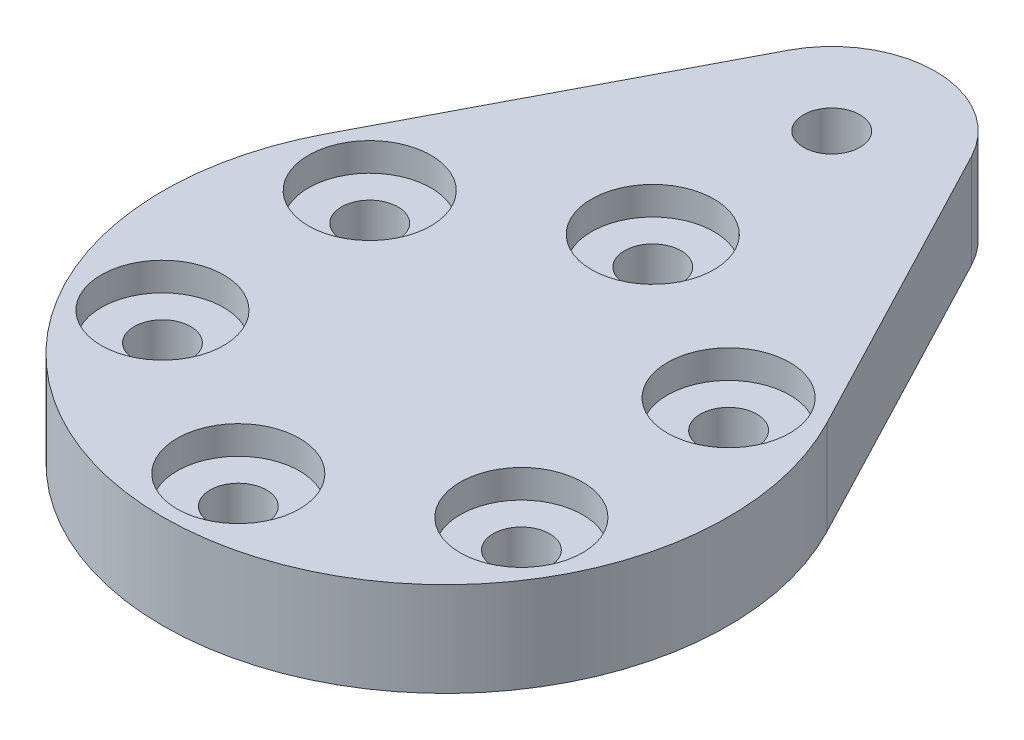
SolidWorks part; units mm, degrees
ref_plane "Front Plane" through (0, 0, 0) normal (0, 0, 1) x (1, 0, 0)
ref_plane "Top Plane" through (0, 0, 0) normal (0, 1, 0) x (1, 0, 0)
ref_plane "Right Plane" through (0, 0, 0) normal (1, 0, 0) x (0, 0, -1)
sketch "Sketch4" plane through (0, 0, 0) normal (0, 1, 0) x (1, 0, 0)
  line L0 (0, 0) -> (0, 20.5) construction
  line L1 (-4.8738, 23.0488) -> (-13.2921, 6.9512)
  line L2 (4.8738, 23.0488) -> (13.2921, 6.9512)
  circle A0 centre (0, 0) radius 11 construction
  circle A1 centre (0, 0) radius 15
  circle A2 centre (0, 11) radius 1.5
  circle A3 centre (9.5263, 5.5) radius 1.5
  circle A4 centre (9.5263, -5.5) radius 1.5
  circle A5 centre (0, -11) radius 1.5
  circle A6 centre (-9.5263, -5.5) radius 1.5
  circle A7 centre (-9.5263, 5.5) radius 1.5
  circle A8 centre (0, 20.5) radius 1.5
  circle A9 centre (0, 20.5) radius 5.5
  point P18 (0, 0)
  dimension "D1" = 22
  dimension "D2" = 30
  dimension "D3" = 3
  dimension "D6" = 3
  dimension "D5" = 20.5
  dimension "D4" = 6
extrude "Boss-Extrude1" add sketch "Sketch4" along normal blind 5 contours A9 A8 | A9 L1 A1 | A9 A1 L2 | A1 A7 A6 A5 A4 A3 A2 region at (-6.7798, 0, -15.4196) region at (0, 0, -25.8444) region at (0, 0, 0) region at (6.7798, 0, -15.4196)
sketch "Sketch6" plane through (0, 5, 0) normal (0, 1, 0) x (1, 0, 0)
  circle A0 centre (0, 0) radius 11 construction
  circle A1 centre (0, 11) radius 3.25
  circle A2 centre (9.5263, 5.5) radius 3.25
  circle A3 centre (9.5263, -5.5) radius 3.25
  circle A4 centre (0, -11) radius 3.25
  circle A5 centre (-9.5263, -5.5) radius 3.25
  circle A6 centre (-9.5263, 5.5) radius 3.25
  point P6 (0, 0)
  point P19 (0, 0)
  dimension "D1" = 6.5
  dimension "D3" = 22
  dimension "D2" = 6
extrude "Cut-Extrude1" cut sketch "Sketch6" against normal blind 1.5
